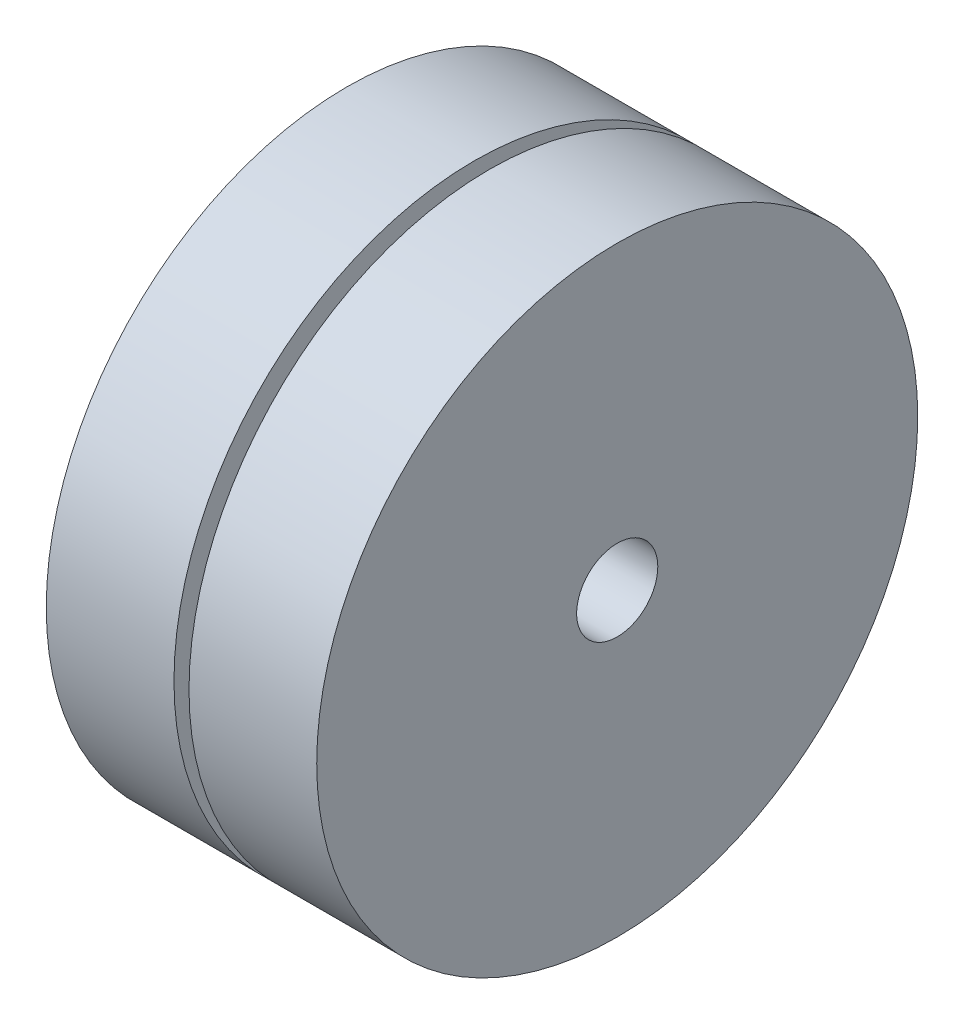
SolidWorks part; units mm, degrees
ref_plane "Front Plane" through (0, 0, 0) normal (0, 0, 1) x (1, 0, 0)
ref_plane "Top Plane" through (0, 0, 0) normal (0, 1, 0) x (1, 0, 0)
ref_plane "Right Plane" through (0, 0, 0) normal (1, 0, 0) x (0, 0, -1)
sketch "Sketch1" plane through (0, 0, 0) normal (1, 0, 0) x (0, 0, -1)
  circle A0 centre (0, 0) radius 20
  dimension "D1" = 40
extrude "Boss-Extrude1" add sketch "Sketch1" along normal blind 18
sketch "Sketch2" plane through (18, 0, 0) normal (1, 0, 0) x (0, 0, -1)
  circle A0 centre (0, 0) radius 2.7
  dimension "D1" = 5.4
extrude "Cut-Extrude1" cut sketch "Sketch2" against normal blind 18
sketch "Sketch3" plane through (0, 0, 0) normal (0, 0, 1) x (1, 0, 0)
  line L0 (0, 0) -> (18, 0) construction
  line L1 (18, -20) -> (18, 20) construction
  line L2 (9, 0) -> (9, 12.3325) construction
  line L3 (8.5, 12.3325) -> (9.5, 12.3325) construction
  line L4 (9.5, 12.3325) -> (9.5, 31.9767)
  line L5 (8.5, 12.3325) -> (8.5, 31.9767)
  line L6 (8.5, 31.9767) -> (9.5, 31.9767)
  line L7 (9, 12.3325) -> (9, 22.9096) construction
  line L8 (18, 20) -> (0, 20) construction
  arc A0 (8.5, 12.3325) -> (9.5, 12.3325) centre (9, 12.3325) ccw construction
  arc A1 (9.5, 12.3325) -> (8.5, 12.3325) centre (9, 12.3325) cw
  point P10 (9, 12.3325)
  point P17 (9, 31.9767)
  dimension "D1" = 1
  dimension "D2" = 0
ref_axis "Axis1" through (0, 0, 0) along (1, 0, 0)
revolve "Cut-Revolve1" cut sketch "Sketch3" angle 360 about L0
fillet "Fillet1" radius 1 rebuild error yes
fillet "Fillet2" radius 2 rebuild error yes
